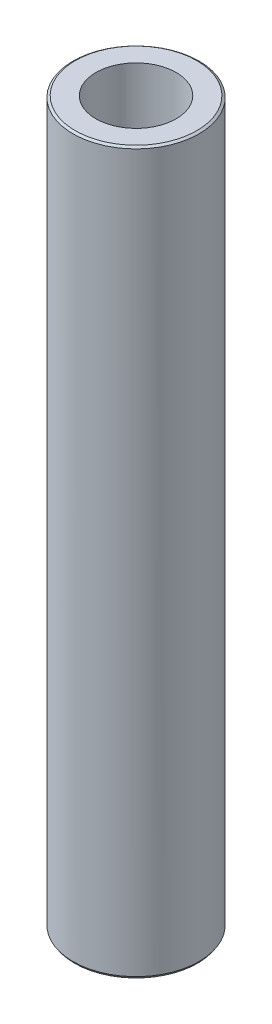
SolidWorks part; units mm, degrees
ref_plane "Front Plane" through (0, 0, 0) normal (0, 0, 1) x (1, 0, 0)
ref_plane "Top Plane" through (0, 0, 0) normal (0, 1, 0) x (1, 0, 0)
ref_plane "Right Plane" through (0, 0, 0) normal (1, 0, 0) x (0, 0, -1)
sketch "Sketch1" plane through (0, 0, 0) normal (0, 1, 0) x (1, 0, 0)
  circle A0 centre (0, 0) radius 52.5
  dimension "SHAFT_OD" = 105
extrude "Boss-Extrude1" add sketch "Sketch1" along normal blind 600
sketch "Sketch2" plane through (0, 0, 0) normal (0, 1, 0) x (1, 0, 0)
  circle A0 centre (0, 0) radius 33.4185
  dimension "BORE_D" = 66.8371
extrude "Cut-Extrude1" cut sketch "Sketch2" along normal through all
chamfer "Chamfer1" distance 1.2913 angle 56.215 2 edges at (0, 600, 52.5) (0, 0, 52.5) first distance on face at (0, 600, 52.5) first distance on face at (0, 0, 33.4185)
